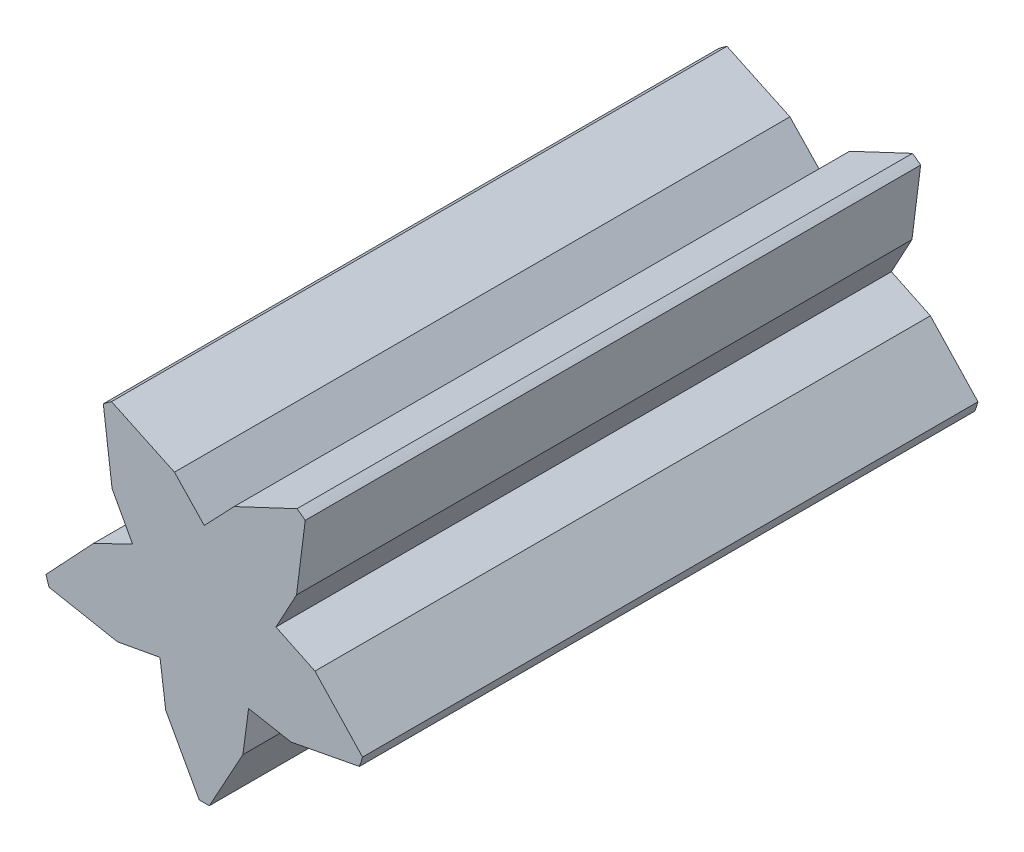
SolidWorks part; units mm, degrees
ref_plane "Front Plane" through (0, 0, 0) normal (0, 0, 1) x (1, 0, 0)
ref_plane "Top Plane" through (0, 0, 0) normal (0, 1, 0) x (1, 0, 0)
ref_plane "Right Plane" through (0, 0, 0) normal (1, 0, 0) x (0, 0, -1)
sketch "Sketch1" plane through (0, 0, 0) normal (0, 0, 1) x (1, 0, 0)
  line L1 (1.7678, -1.7678) -> (-1.7678, -1.7678) construction
  line L2 (1.7678, -1.7678) -> (1.7678, 1.7678) construction
  line L3 (1.7678, 1.7678) -> (-1.7678, 1.7678) construction
  line L4 (-1.7678, -1.7678) -> (-1.7678, 1.7678) construction
  line L5 (1.7678, -1.7678) -> (-1.7678, 1.7678) construction
  line L6 (1.7678, 1.7678) -> (-1.7678, -1.7678) construction
  circle A0 centre (0, 0) radius 7.5
  circle A1 centre (0, 0) radius 2.5 construction
  dimension "D1" = 15
  dimension "D2" = 5
extrude "Boss-Extrude1" add sketch "Sketch1" along normal blind 28
sketch "Sketch2" plane through (0, 0, 0) normal (0, 0, 1) x (1, 0, 0)
  line L0 (0, 0) -> (0, 10.088) construction
  line L1 (0, 3.4293) -> (-1.3565, 4.8529)
  line L2 (-1.3565, 4.8529) -> (-4.2191, 6.2007)
  line L3 (-4.2191, 6.2007) -> (0, 11.2516)
  line L4 (4.2191, 6.2007) -> (0, 11.2516)
  line L5 (1.3565, 4.8529) -> (4.2191, 6.2007)
  line L6 (0, 3.4293) -> (1.3565, 4.8529)
  circle A14 centre (0, 0) radius 7.5 construction
  point P8 (-1.4604, 4.3216)
  point P9 (-3.4274, 6.671)
  point P11 (-1.3565, 4.8529)
  point P12 (-4.2191, 6.2007)
  point P13 (0, 11.2516)
  point P16 (0, 7.5)
extrude "Cut-Extrude1" cut sketch "Sketch2" along normal through all
pattern_circular "CirPattern1" count 5 over 360 about axis through (0, 0, 28) along (0, 0, -1) of "Cut-Extrude1" reverse direction yes
sketch "Sketch3" plane through (0, 0, 0) normal (0, 0, 1) x (1, 0, 0)
  circle A0 centre (0, 0) radius 7.5
  dimension "D1" = 15
